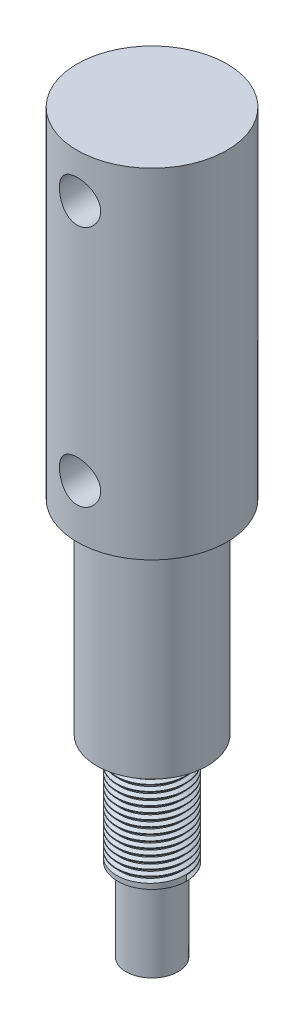
SolidWorks part; units mm, degrees
material "AISI 316 Annealed Stainless Steel Bar (SS)"
ref_plane "Front Plane" through (0, 0, 0) normal (0, 0, 1) x (1, 0, 0)
ref_plane "Top Plane" through (0, 0, 0) normal (0, 1, 0) x (1, 0, 0)
ref_plane "Right Plane" through (0, 0, 0) normal (1, 0, 0) x (0, 0, -1)
sketch "Sketch2" plane through (0, 0, 0) normal (0, 0, 1) x (1, 0, 0)
  line L0 (0, 0) -> (0, 508.8276) construction
  line L1 (0, 0) -> (6, 0)
  line L2 (0, 0) -> (0, 19.05)
  line L3 (0, 19.05) -> (6, 19.05)
  line L4 (6, 0) -> (6, 19.05)
  line L5 (0, 19.05) -> (7.9375, 19.05)
  line L6 (0, 19.05) -> (0, 44.45)
  line L7 (0, 44.45) -> (7.9375, 44.45)
  line L8 (7.9375, 19.05) -> (7.9375, 44.45)
  line L9 (0, 44.45) -> (12.721, 44.45)
  line L10 (0, 44.45) -> (0, 91.44)
  line L11 (0, 91.44) -> (12.721, 91.44)
  line L12 (12.721, 44.45) -> (12.721, 91.44)
  line L13 (0, 91.44) -> (17.272, 91.44)
  line L14 (0, 91.44) -> (0, 169.672)
  line L15 (0, 169.672) -> (17.272, 169.672)
  line L16 (17.272, 91.44) -> (17.272, 169.672)
  dimension "D1" = 78.232
  dimension "D2" = 17.272
  dimension "D4" = 46.99
  dimension "D3" = 12.721
  dimension "D5" = 25.4
  dimension "D6" = 7.9375
  dimension "D7" = 19.05
  dimension "D8" = 6
revolve "Revolve1" add sketch "Sketch2" angle 360 about L0 region at (3, 9.525, 0) region at (3.9687, 31.75, 0) region at (6.3605, 67.945, 0) region at (8.636, 130.556, 0)
thread "Thread2" pitch 1.4111 method cut profile "Thread Profile3" start angle 0, offset 0, length 0, pitch 1.4111, diameter 15.875
ref_plane "Plane3" through (7.9375, 19.05, 0) normal (0, 0, 1) x (1, 0, 0)
sketch "Thread Profile3" plane through (7.9375, 19.05, 0) normal (0, 0, 1) x (1, 0, 0)
  line L0 (0, 0) -> (0, 1.4111) construction
  line L11 (0, 0) -> (0, 1.2347)
  line L12 (0, 1.2347) -> (-0.7638, 0.7937)
  line L13 (-0.7638, 0.7937) -> (-0.7638, 0.441)
  line L15 (-0.7638, 0.441) -> (0, 0)
  line L17 (-0.7638, 0.6174) -> (0, 0.6174) construction
  point P2 (0, 0)
  dimension "Pitch" = 1.4111
  dimension "Profile_Angle" = 60
  dimension "Profile_Land" = 0.3528
  dimension "Profile_Height" = 0.7638
sketch "Sketch3" plane through (0, 0, 0) normal (0, 0, 1) x (1, 0, 0)
  line L0 (0, 0) -> (0, 197.3408) construction
  line L1 (17.272, 169.672) -> (-17.272, 169.672) construction
  circle A0 centre (0, 159.512) radius 4.7625
  circle A1 centre (0, 103.632) radius 4.7625
  dimension "D1" = 9.525
  dimension "D2" = 10.16
  dimension "D3" = 66.04
extrude "Cut-Extrude1" cut sketch "Sketch3" against normal through all both and the other way through all
equation "\"hole diamiter\"= 1.36in"
equation "\"wheel depth\"= 2.88"
equation "\"press_tolerance\"= 0.00165"
equation "\"wheel_connection\"= \"hole diamiter\"'https://at-machining.com/tolerance-press-fit/"
equation "\"D1@Sketch2\"=\"wheel depth\"+0.2"
equation "\"D2@Sketch2\"=\"wheel_connection\"/2"
equation "\"fitting depth\"= 1.85"
equation "\"D4@Sketch2\"=\"fitting depth\""
equation "\"bearing_id\"= 1"
equation "\"bearing_connection\"= \"bearing_id\" + \"press_tolerance\"'https://at-machining.com/tolerance-press-fit/"
equation "\"D3@Sketch2\"=\"bearing_connection\"/2"
equation "\"thread length\"= 1"
equation "\"major_diamiter\"= 5 / 8'https://www.machiningdoctor.com/threadinfo/?tid=81"
equation "\"D5@Sketch2\"=\"thread length\""
equation "\"D6@Sketch2\"=\"major_diamiter\"/2"
equation "\"coupling diamiter\"= 12mm"
equation "\"coupling lenght\"= 1.5 / 2"
equation "\"D7@Sketch2\"=\"coupling lenght\""
equation "\"D8@Sketch2\"=\"coupling diamiter\"/2"
